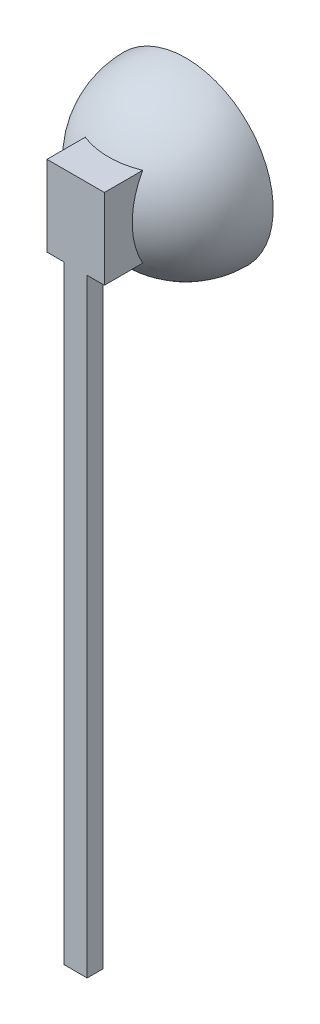
SolidWorks part; units mm, degrees
ref_plane "Front Plane" through (0, 0, 0) normal (0, 0, 1) x (1, 0, 0)
ref_plane "Top Plane" through (0, 0, 0) normal (0, 1, 0) x (1, 0, 0)
ref_plane "Right Plane" through (0, 0, 0) normal (1, 0, 0) x (0, 0, -1)
sketch "Sketch1" plane through (0, 0, 0) normal (0, 0, 1) x (1, 0, 0)
  line L0 (0, 33) -> (0, -33) construction
  line L1 (0, 38) -> (0, 33)
  line L2 (0, -33) -> (0, -38)
  arc A0 (0, -33) -> (0, 33) centre (0, 0) ccw
  arc A1 (0, -38) -> (0, 38) centre (0, 0) ccw
revolve "Revolve1" add sketch "Sketch1" angle 180 about L2
ref_plane "Plane1" through (0, 0, 38) normal (0, 0, -1) x (-1, 0, 0)
sketch "Sketch2" plane through (0, 0, 38) normal (0, 0, -1) x (-1, 0, 0)
  line L1 (-12.5, -17.5) -> (12.5, -17.5)
  line L2 (-12.5, -17.5) -> (-12.5, 17.5)
  line L3 (-12.5, 17.5) -> (12.5, 17.5)
  line L4 (12.5, -17.5) -> (12.5, 17.5)
  line L5 (-12.5, -17.5) -> (12.5, 17.5) construction
  line L6 (-12.5, 17.5) -> (12.5, -17.5) construction
  point P0 (0, 0)
  dimension "D1" = 35
  dimension "D2" = 25
extrude "Boss-Extrude2" add sketch "Sketch2" along normal up to body and the other way blind 10 separate body
sketch "Sketch5" plane through (0, 0, 48) normal (0, 0, 1) x (1, 0, 0)
  line L0 (-12.5, 17.5) -> (12.5, 17.5) construction
  line L4 (-5, 17.5) -> (5, 17.5)
  line L5 (0, -3.0387) -> (0, 296.9613) construction
  line L8 (-5, 17.5) -> (-5, -282.5)
  line L9 (-5, -282.5) -> (5, -282.5)
  line L10 (5, 17.5) -> (5, -282.5)
  dimension "D1" = 10
  dimension "D3" = 300
extrude "Boss-Extrude3" add sketch "Sketch5" against normal blind 7
sketch "Sketch6" plane through (0, -282.5, 0) normal (0, -1, 0) x (-1, 0, 0)
  line L0 (-5, -41) -> (-5, -48) construction
  line L1 (-3.5, -42.25) -> (3.5, -42.25)
  line L2 (-3.5, -42.25) -> (-3.5, -46.75)
  line L3 (-3.5, -46.75) -> (3.5, -46.75)
  line L4 (3.5, -42.25) -> (3.5, -46.75)
  line L5 (-5, -41) -> (5, -41) construction
  line L6 (5, -41) -> (5, -48) construction
  line L7 (5, -48) -> (-5, -48) construction
  dimension "D1" = 1.5
  dimension "D2" = 1.25
  dimension "D3" = 1.5
  dimension "D4" = 1.25
extrude "Cut-Extrude1" cut sketch "Sketch6" against normal blind 265
sketch "Sketch7" plane through (0, 0, 0) normal (1, 0, 0) x (0, 0, -1)
  point P5 (-44.5, 0)
